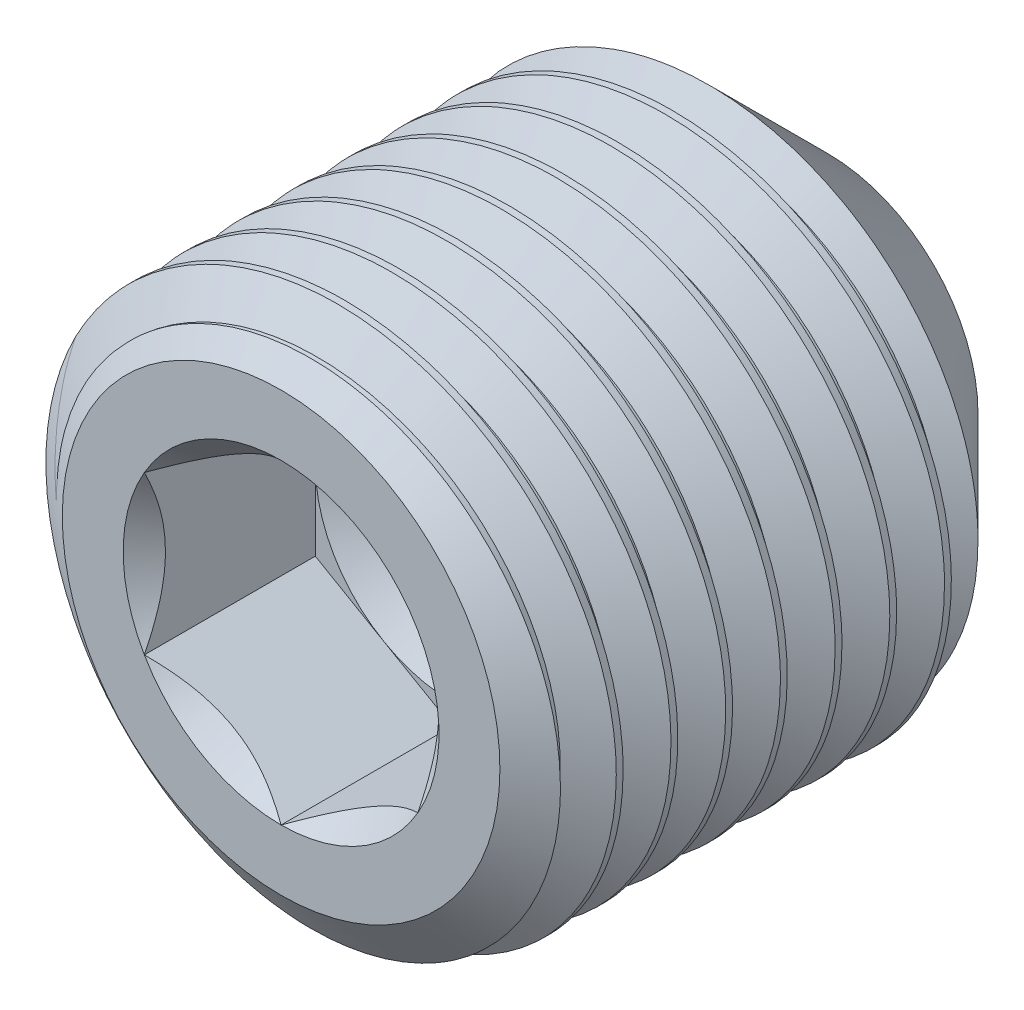
SolidWorks part; units mm, degrees
material "Alloy Steel"
ref_plane "Front" through (0, 0, 0) normal (0, 0, 1) x (1, 0, 0)
ref_plane "Top" through (0, 0, 0) normal (0, 1, 0) x (1, 0, 0)
ref_plane "Right" through (0, 0, 0) normal (1, 0, 0) x (0, 0, -1)
sketch "Sketch22" plane through (0, 0, 0) normal (1, 0, 0) x (0, 0, -1)
  line L0 (-5.3046, 0) -> (-5.3046, 5.08)
  line L1 (-5.3046, 5.08) -> (-4.4154, 6.35)
  line L2 (-4.4154, 6.35) -> (4.5249, 6.35)
  line L3 (4.5249, 6.35) -> (7.3954, 3.4796)
  line L4 (7.3954, 3.4796) -> (5.3046, 0)
  line L5 (5.3046, 0) -> (-5.3046, 0)
  line L6 (5.3046, 0) -> (7.3954, 0) construction
  line L7 (7.3954, 0) -> (7.3954, 3.4796) construction
  line L8 (7.3954, -3.4796) -> (5.3046, 0) construction
  line L9 (-4.4154, -6.35) -> (4.5249, -6.35) construction
  dimension "Dia" = 12.7
  dimension "Length" = 12.7
  dimension "D3" = 35
  dimension "D5" = 118
  dimension "D6" = 45
  dimension "D7" = 10.16
revolve "Revolve1" add sketch "Sketch22" angle 360 about L6
ref_plane "Plane1" through (0, 0, -7.3954) normal (0, 0, 1) x (1, 0, 0)
sketch "Sketch27" plane through (0, 0, -7.3954) normal (0, 0, 1) x (1, 0, 0)
  circle A0 centre (0, 0) radius 6.35 construction
  circle A1 centre (0, 0) radius 6.35
curve "Helix/Spiral1" pitch 1.27 height 13.97 radius 6.35 centre (0, 0, -7.3954) axis (0, 0, 1) start towards (0, 1, 0)
sketch "Sketch28" plane through (0, 0, 0) normal (1, 0, 0) x (0, 0, -1)
  line L0 (7.3954, 6.35) -> (8.5066, 6.35)
  line L1 (8.5066, 6.35) -> (8.0304, 5.5251)
  line L2 (8.0304, 5.5251) -> (7.8716, 5.5251)
  line L3 (7.8716, 5.5251) -> (7.3954, 6.35)
  line L4 (7.6335, 5.9376) -> (8.2685, 5.9376) construction
  line L6 (-4.4154, 6.35) -> (4.5249, 6.35) construction
  line L7 (7.3954, 6.985) -> (7.3954, -6.985) construction
  dimension "D1" = 0.1588
  dimension "D3" = 60
  dimension "D2" = 0.635
sweep "Cut-Sweep2" cut profiles "Sketch28" path "Helix/Spiral1" align with end faces yes
sketch "Sketch23" plane through (0, 0, 5.3046) normal (0, 0, 1) x (1, 0, 0)
  line L1 (0, 3.6662) -> (-3.175, 1.8331)
  line L2 (-3.175, 1.8331) -> (-3.175, -1.8331)
  line L3 (-3.175, -1.8331) -> (0, -3.6662)
  line L4 (0, -3.6662) -> (3.175, -1.8331)
  line L5 (3.175, -1.8331) -> (3.175, 1.8331)
  line L6 (3.175, 1.8331) -> (0, 3.6662)
  circle A0 centre (0, 0) radius 3.175 construction
  dimension "Hex" = 6.35
extrude "Cut-Extrude10" cut sketch "Sketch23" against normal blind 3.9688
sketch "Sketch24" plane through (0, 0, 5.3046) normal (0, 0, 1) x (1, 0, 0)
  circle A0 centre (0, 0) radius 3.6662
extrude "Cut-Extrude11" cut sketch "Sketch24" against normal through all draft 45
sketch "Sketch26" plane through (0, 0, 1.3359) normal (0, 0, 1) x (1, 0, 0)
  circle A0 centre (0, 0) radius 3.175 construction
  circle A1 centre (0, 0) radius 3.175
extrude "Cut-Extrude12" cut sketch "Sketch26" against normal through all draft 60
sketch "Sketch30" plane through (0, 0, 0) normal (1, 0, 0) x (0, 0, -1)
  line L0 (-4.4154, 6.35) -> (4.5249, 6.35) construction
  line L1 (-5.3046, 0) -> (-5.3046, 5.08) construction
  line L2 (7.3954, 0) -> (7.3954, 3.4796) construction
  line L3 (-4.4154, -6.35) -> (4.5249, -6.35) construction
  point P0 (-5.3046, 6.35)
  point P1 (7.3954, 6.35)
  point P2 (7.3954, -6.35)
  point P11 (4.2204, -6.35)
  dimension "D1" = 3.175
sketch "Sketch31" plane through (0, 0, 0) normal (1, 0, 0) x (0, 0, -1)
  line L2 (5.3046, 0) -> (7.3954, -3.4796)
  line L3 (7.3954, 3.4796) -> (5.3046, 0)
equation "\"D7@Sketch22\"=\"Dia@Sketch22\"*.8"
equation "\"D1@Sketch28\" = \"D4@Helix/Spiral1\" * .125"
equation "\"D3@Helix/Spiral1\" = \"Length@Sketch22\" + \"D4@Helix/Spiral1\""
equation "\"D1@Sketch30\" = \"D4@Helix/Spiral1\" * 2.5"
equation "\"hex Depth@Cut-Extrude10\" = \"Hex@Sketch23\" * .625"
equation "\"D2@Sketch28\" = \"D4@Helix/Spiral1\" * .5"
